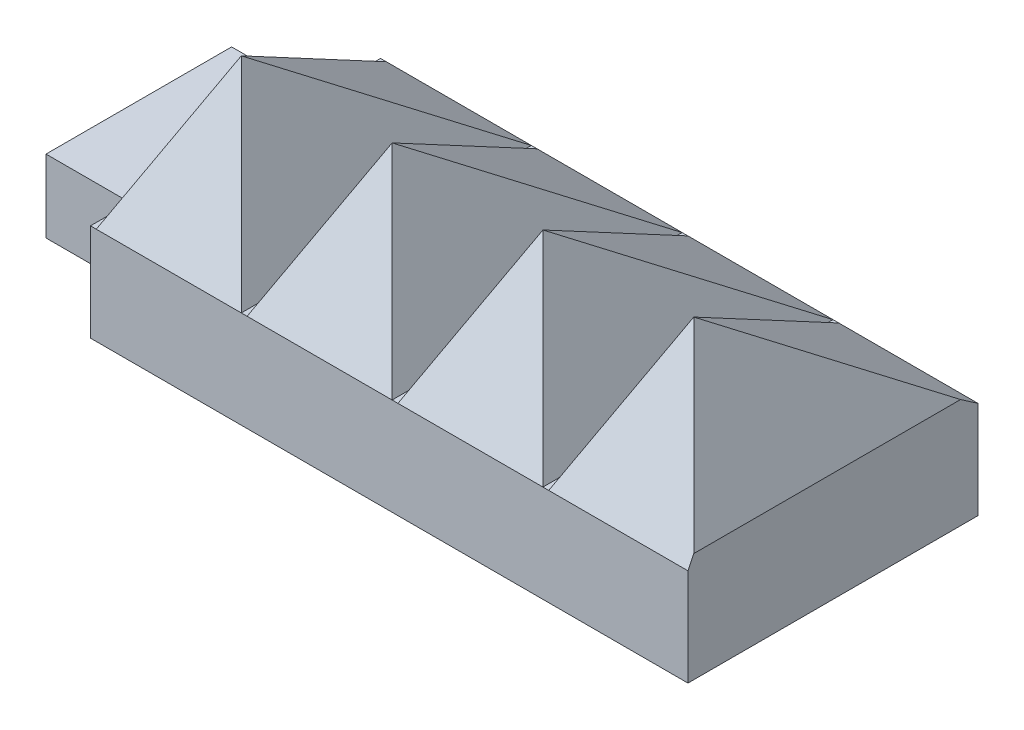
SolidWorks part; units mm, degrees
ref_plane "Front Plane" through (0, 0, 0) normal (0, 0, 1) x (1, 0, 0)
ref_plane "Top Plane" through (0, 0, 0) normal (0, 1, 0) x (1, 0, 0)
ref_plane "Right Plane" through (0, 0, 0) normal (1, 0, 0) x (0, 0, -1)
sketch "Sketch1" plane through (0, 0, 0) normal (0, 1, 0) x (1, 0, 0)
  line L1 (0, 0) -> (19.05, 0)
  line L2 (0, 0) -> (0, -19.05)
  line L3 (0, -19.05) -> (19.05, -19.05)
  line L4 (19.05, 0) -> (19.05, -19.05)
extrude "Boss-Extrude2" add sketch "Sketch1" along normal blind 6.35
ref_plane "Plane2" through (0, 26.0731, 0) normal (0, 1, 0) x (1, 0, 0)
sketch "Sketch8" plane through (0, 0, 0) normal (0, 1, 0) x (1, 0, 0)
  line L9 (0, 9.525) -> (217.17, 9.525)
  line L10 (0, 9.525) -> (0, -28.575)
  line L11 (0, -28.575) -> (217.17, -28.575)
  line L12 (217.17, 9.525) -> (217.17, -28.575)
extrude "Boss-Extrude4" add sketch "Sketch8" along normal blind 6.35 contours L11 L12 L9 L10
extrude "Boss-Extrude5" add sketch "Sketch8<5>" against normal blind 6.4262 contours L11 L12 L9 L10
sketch "Sketch8<5>" plane through (0, 0, 0) normal (0, 1, 0) x (1, 0, 0) same geometry as "Sketch8"
sketch "Sketch9" plane through (0, 6.35, 0) normal (0, 1, 0) x (1, 0, 0)
  line L0 (0, -28.575) -> (217.17, -28.575) construction
  line L1 (0, 9.525) -> (19.05, 9.525)
  line L2 (0, 9.525) -> (0, -28.575)
  line L3 (0, -28.575) -> (19.05, -28.575)
  line L4 (19.05, 9.525) -> (19.05, -28.575)
sketch "Sketch13" plane through (0, 6.35, 0) normal (0, 1, 0) x (1, 0, 0)
  line L0 (0, -9.525) -> (19.05, -28.575)
  line L1 (0, 9.525) -> (0, -28.575) construction
  line L2 (19.05, -28.575) -> (19.05, -9.525)
  line L3 (19.05, 9.525) -> (19.05, -28.575) construction
  line L4 (19.05, -9.525) -> (0, -28.575)
ref_plane "Plane4" through (0, 26.0731, 0) normal (0, 1, 0) x (1, 0, 0)
sketch "Sketch14" plane through (0, 26.0731, 0) normal (0, 1, 0) x (1, 0, 0)
  line L0 (0, -9.525) -> (19.05, -28.575) construction
  point P0 (9.525, -19.05)
loft "Loft3" add profiles "Sketch9", "Sketch14"
pattern_linear "LPattern3" count 11 spacing 19.812 along (1, 0, 0) of "Loft3"
sketch "Sketch15" plane through (0, -6.4262, 0) normal (0, -1, 0) x (1, 0, 0)
  line L0 (217.17, -9.525) -> (217.17, 28.575) construction
  line L1 (0, -9.525) -> (0, 28.575) construction
  circle A0 centre (179.07, 9.525) radius 12.192
  circle A1 centre (38.1, 9.525) radius 12.192
  circle A2 centre (108.585, 9.525) radius 12.192
  dimension "D1" = 38.1
  dimension "D2" = 70.485
  dimension "D3" = 38.1
  dimension "D4" = 24.384
  dimension "D5" = 24.384
  dimension "D6" = 24.384
extrude "Boss-Extrude6" add sketch "Sketch15" along normal blind 6.35
ref_plane "Plane5" through (219.71, 0, 0) normal (1, 0, 0) x (0, 0, -1)
sketch "Sketch16" plane through (219.71, 0, 0) normal (1, 0, 0) x (0, 0, -1)
  line L1 (-28.575, -6.4262) -> (9.525, -6.4262)
  line L2 (-28.575, -6.4262) -> (-28.575, 15.6471)
  line L3 (-28.575, 15.6471) -> (9.525, 15.6471)
  line L4 (9.525, -6.4262) -> (9.525, 15.6471)
extrude "Cut-Extrude1" cut sketch "Sketch16" against normal blind 3.302 contours L3 L4 L1 L2
sketch "Sketch17" plane through (0, 0, 0) normal (-1, 0, 0) x (0, 0, 1)
  line L1 (-21.3546, 29.7888) -> (40.2896, 29.7888)
  line L2 (-21.3546, 29.7888) -> (-21.3546, -16.6337)
  line L3 (-21.3546, -16.6337) -> (40.2896, -16.6337)
  line L4 (40.2896, 29.7888) -> (40.2896, -16.6337)
extrude "Cut-Extrude2" cut sketch "Sketch17" against normal up to vertex (137.922 mm away) up to point (137.922, 6.35, 28.575)
sketch "Sketch18" plane through (137.922, 0, 0) normal (-1, 0, 0) x (0, 0, 1)
  line L4 (-2.667, -4.8133) -> (21.717, -4.8133)
  line L5 (-2.667, -4.8133) -> (-2.667, 4.7371)
  line L6 (-2.667, 4.7371) -> (21.717, 4.7371)
  line L7 (21.717, -4.8133) -> (21.717, 4.7371)
  line L8 (-2.667, -4.8133) -> (21.717, 4.7371) construction
  line L9 (-2.667, 4.7371) -> (21.717, -4.8133) construction
  point P6 (9.525, -0.0381)
  dimension "D1" = 24.384
  dimension "D2" = 9.5504
extrude "Boss-Extrude7" add sketch "Sketch18" along normal blind 12.7
